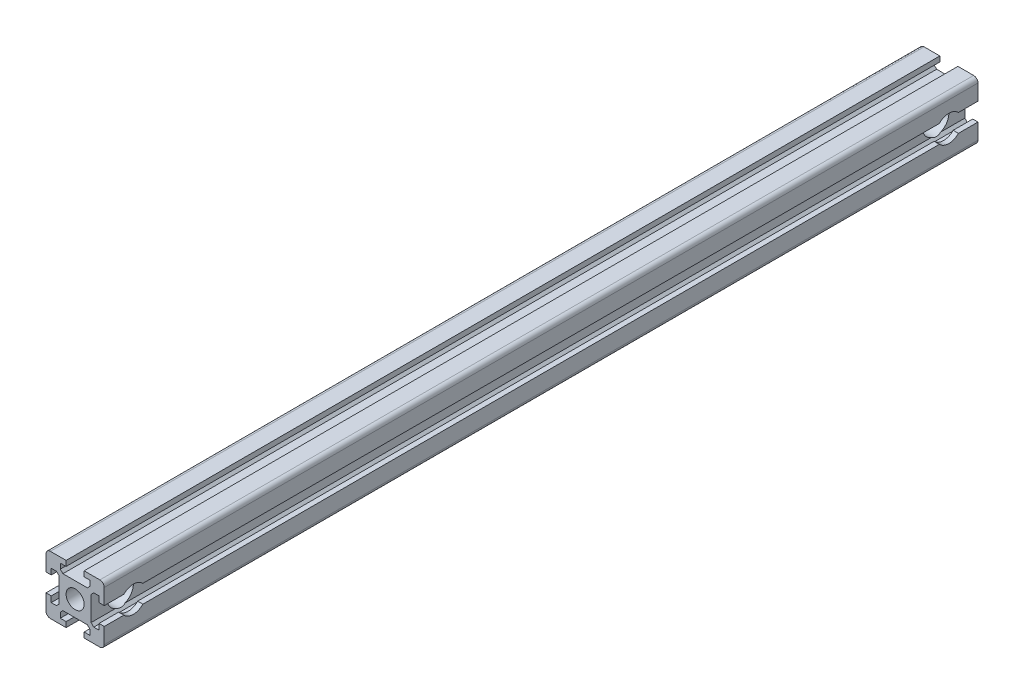
SolidWorks part; units mm, degrees
material "6061 Alloy"
ref_plane "Front Plane" through (0, 0, 0) normal (0, 0, 1) x (1, 0, 0)
ref_plane "Top Plane" through (0, 0, 0) normal (0, 1, 0) x (1, 0, 0)
ref_plane "Right Plane" through (0, 0, 0) normal (1, 0, 0) x (0, 0, -1)
sketch "Sketch1" plane through (0, 0, 0) normal (0, 0, 1) x (1, 0, 0)
  line L0 (-10, 3.1) -> (-8.2, 3.1)
  line L1 (-8.5, 10) -> (-3.1, 10) construction
  line L2 (-10, 8.5) -> (-10, 3.1) construction
  line L3 (-10, -3.1) -> (-10, -8.5) construction
  line L4 (-8.5, -10) -> (-3.1, -10) construction
  line L5 (-10, -3.1) -> (-10, -8.5)
  line L6 (-8.5, -10) -> (-3.1, -10)
  line L7 (-8.2, 3.1) -> (-8.2, 5.1)
  line L8 (-8.2, 5.1) -> (-6.4, 5.1)
  line L9 (-10, -3.1) -> (-8.2, -3.1)
  line L10 (-8.2, -3.1) -> (-8.2, -5.1)
  line L11 (-8.2, -5.1) -> (-6.4, -5.1)
  line L13 (-6.4, 5.1) -> (-5.4929, 4.1929)
  line L14 (-5.4929, 4.1929) -> (-5.4929, -4.1929)
  line L15 (-6.4, -5.1) -> (-5.4929, -4.1929)
  line L16 (-3.1, 10) -> (-3.1, 8.2)
  line L17 (-3.1, 8.2) -> (-5.1, 8.2)
  line L19 (-5.1, 8.2) -> (-5.1, 6.4)
  line L20 (-5.1, 6.4) -> (-4.1929, 5.4929)
  line L21 (-4.1929, 5.4929) -> (4.1929, 5.4929)
  line L22 (4.1929, 5.4929) -> (5.1, 6.4)
  line L23 (5.1, 6.4) -> (5.1, 8.2)
  line L24 (5.1, 8.2) -> (3.1, 8.2)
  line L25 (3.1, 8.2) -> (3.1, 10)
  line L26 (-3.1, -10) -> (-3.1, -8.2)
  line L27 (-3.1, -8.2) -> (-5.1, -8.2)
  line L28 (-5.1, -8.2) -> (-5.1, -6.4)
  line L29 (-5.1, -6.4) -> (-4.1929, -5.4929)
  line L30 (-4.1929, -5.4929) -> (4.1929, -5.4929)
  line L31 (4.1929, -5.4929) -> (5.1, -6.4)
  line L32 (5.1, -6.4) -> (5.1, -8.2)
  line L33 (5.1, -8.2) -> (3.1, -8.2)
  line L34 (3.1, -8.2) -> (3.1, -10)
  line L35 (3.1, -10) -> (8.5, -10)
  line L36 (10, -8.5) -> (10, -3.1)
  line L37 (10, -3.1) -> (8.2, -3.1)
  line L38 (8.2, -3.1) -> (8.2, -5.1)
  line L39 (8.2, -5.1) -> (6.4, -5.1)
  line L40 (6.4, -5.1) -> (5.4929, -4.1929)
  line L41 (5.4929, -4.1929) -> (5.4929, 4.1929)
  line L42 (5.4929, 4.1929) -> (6.4, 5.1)
  line L43 (6.4, 5.1) -> (8.2, 5.1)
  line L44 (8.2, 5.1) -> (8.2, 3.1)
  line L45 (8.2, 3.1) -> (10, 3.1)
  line L46 (10, 3.1) -> (10, 8.5)
  line L47 (8.5, 10) -> (3.1, 10)
  line L48 (-3.1, 10) -> (-8.5, 10)
  line L49 (-10, 8.5) -> (-10, 3.1)
  arc A0 (-8.5, 10) -> (-10, 8.5) centre (-8.5, 8.5) ccw
  arc A1 (-10, -8.5) -> (-8.5, -10) centre (-8.5, -8.5) ccw construction
  arc A2 (8.5, -10) -> (10, -8.5) centre (8.5, -8.5) ccw
  arc A3 (8.5, 10) -> (10, 8.5) centre (8.5, 8.5) cw
  arc A4 (-8.5, -10) -> (-10, -8.5) centre (-8.5, -8.5) cw
  circle A6 centre (0, 0) radius 3.1
  point P0 (0, 0)
  point P44 (-5.2, -3.4858)
  point P47 (-5.2, 3.4858)
  dimension "D3" = 5.4929
  dimension "D5" = 1.5
  dimension "D1" = 6.2
  dimension "D2" = 5.4929
  dimension "D4" = 1.5
  dimension "D6" = 1.5
extrude "Boss-Extrude1" add sketch "Sketch1" along normal blind 300
sketch "Sketch3" plane through (5.4929, 0, 0) normal (1, 0, 0) x (0, 0, -1)
  line L0 (0, -4.1929) -> (0, 4.1929) construction
  line L1 (-300, -10) -> (0, -10) construction
  line L2 (-300, -4.1929) -> (-300, 4.1929) construction
  circle A0 centre (-10, 0) radius 4.5
  circle A1 centre (-290, 0) radius 4.5
  point P4 (0, 0)
  dimension "D1" = 10
  dimension "D2" = 10
  dimension "D3" = 10
  dimension "D4" = 9
extrude "Cut-Extrude2" cut sketch "Sketch3" against normal blind 11 and the other way through all
